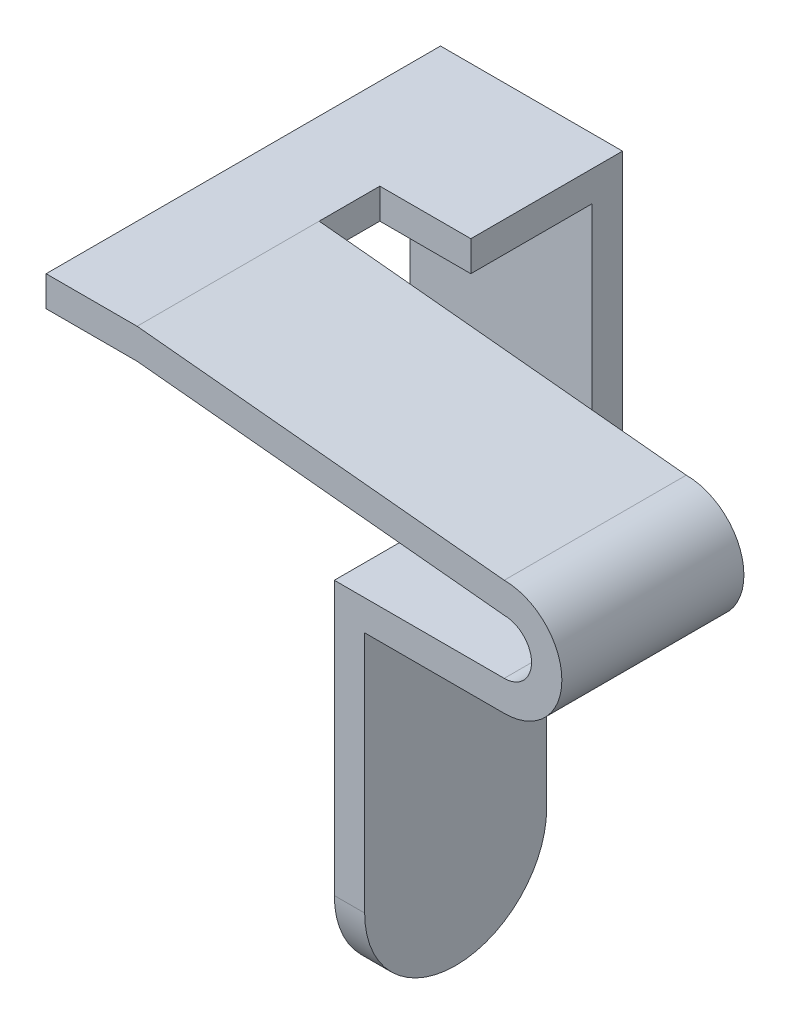
SolidWorks part; units mm, degrees
ref_plane "Front" through (0, 0, 0) normal (0, 0, 1) x (1, 0, 0)
ref_plane "Top" through (0, 0, 0) normal (0, 1, 0) x (1, 0, 0)
ref_plane "Right" through (0, 0, 0) normal (1, 0, 0) x (0, 0, -1)
sketch "Sketch1" plane through (0, 0, 0) normal (0, 0, 1) x (1, 0, 0)
  line L0 (0, 0) -> (1.5, 0)
  line L1 (1.5, 0) -> (7.55, -0.6)
  line L2 (0, 0) -> (0, 0.5)
  line L3 (0, 0.5) -> (1.5, 0.5)
  line L4 (1.5, 0.5) -> (7.55, -0.1)
  line L5 (0, 0.5) -> (8.5, 0.5) construction
  line L6 (8.5, 0.5) -> (8.5, -7.5) construction
  line L7 (4.75, -7.5) -> (5.25, -7.5)
  line L8 (5.25, -7.5) -> (5.25, -2)
  line L9 (5.25, -2) -> (7.55, -2)
  line L10 (8.5, -7.5) -> (5.25, -7.5) construction
  line L11 (7.55, -1.5) -> (4.75, -1.5)
  line L12 (4.75, -1.5) -> (4.75, -7.5)
  line L16 (9, -1.5) -> (0, -1.5) construction
  arc A0 (7.55, -0.1) -> (7.55, -2) centre (7.55, -1.05) cw
  arc A1 (7.55, -0.6) -> (7.55, -1.5) centre (7.55, -1.05) cw
  dimension "D4" = 2.5
  dimension "D1" = 0.5
  dimension "D2" = 3.75
  dimension "D3" = 8.5
  dimension "D5" = 5.5
  dimension "D6" = 0.5
  dimension "D7" = 0.5
  dimension "D8" = 0.6
  dimension "D9" = 1.5
extrude "Boss-Extrude1" add sketch "Sketch1" along normal blind 3
sketch "Sketch3" plane through (0, 0, 0) normal (0, -1, 0) x (-1, 0, 0)
  line L0 (-3, 1) -> (-1.5, 1)
  line L1 (0, 0) -> (-1.5, 0)
  line L2 (0, 0) -> (0, 3.5)
  line L3 (0, 3.5) -> (-3, 3.5)
  line L4 (-3, 3.5) -> (-3, 1)
  line L5 (-1.5, 1) -> (-1.5, 0)
  dimension "D1" = 3.5
  dimension "D2" = 3
  dimension "D3" = 1
  dimension "D4" = 1.5
extrude "Boss-Extrude3" add sketch "Sketch3" against normal blind 0.5
sketch "Sketch4" plane through (0, 0, 0) normal (0, -1, 0) x (1, 0, 0)
  line L0 (3, -3.5) -> (3, -1) construction
  line L1 (0, -3.5) -> (3, -3.5)
  line L2 (0, -3.5) -> (0, -3)
  line L3 (0, -3) -> (3, -3)
  line L4 (3, -3.5) -> (3, -3)
  dimension "D1" = 0.5
extrude "Boss-Extrude5" add sketch "Sketch4" along normal up to surface (7.5 mm away) up to face at (5, -7.5, 1.5)
fillet "Fillet1" radius 1.5 4 edges at (0, -7.5, -3.25) (3, -7.5, -3.25) (5, -7.5, 3) (5, -7.5, 0)
